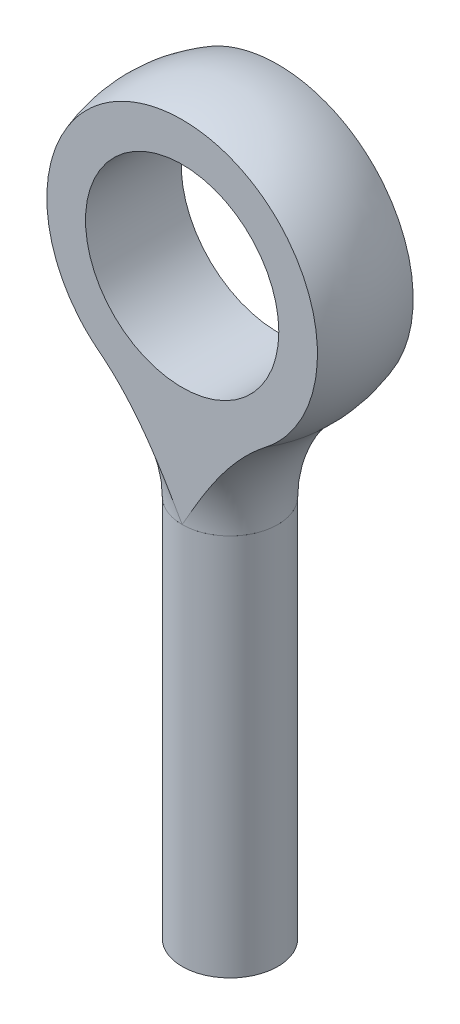
SolidWorks part; units mm, degrees
material "6061 Alloy"
ref_plane "Front" through (0, 0, 0) normal (0, 0, 1) x (1, 0, 0)
ref_plane "Top" through (0, 0, 0) normal (0, 1, 0) x (1, 0, 0)
ref_plane "Right" through (0, 0, 0) normal (1, 0, 0) x (0, 0, -1)
sketch "Sketch1" plane through (0, 0, 0) normal (0, 0, 1) x (1, 0, 0)
  line L0 (0, 0) -> (0, -25.4)
  line L1 (0, -25.4) -> (3.175, -25.4)
  line L2 (3.175, -25.4) -> (3.175, 0)
  line L3 (3.175, 0) -> (0, 0)
  line L5 (0, 23.8125) -> (0, 0) construction
  line L6 (0, 23.8125) -> (9.525, 23.8125) construction
  line L7 (9.525, 23.8125) -> (9.525, 14.2875) construction
  line L8 (-3.175, -25.4) -> (-3.175, 0) construction
  line L9 (3.2732, -25.3433) -> (3.2732, -26.2501)
  line L10 (3.2732, -26.2501) -> (2.4879, -25.7967)
  line L11 (2.586, -25.8534) -> (2.586, -25.74)
  line L12 (2.4879, -25.7967) -> (3.2732, -25.3433)
  line L13 (3.2241, -25.3717) -> (3.2241, -26.2218)
  line L14 (3.2732, -25.7967) -> (3.175, -25.7967)
  line L15 (3.175, -25.4) -> (3.175, -26.1934)
  line L16 (2.4879, -25.7967) -> (2.586, -25.7967)
  arc A0 (6.3827, 7.2174) -> (0, 23.8125) centre (0, 14.2875) ccw construction
  circle A1 centre (0, 14.2875) radius 3.175 construction
  circle A2 centre (0, 14.2875) radius 6.35 construction
  circle A3 centre (0, 14.2875) radius 6.4135 construction
  arc A4 (3.175, 0) -> (6.3827, 7.2174) centre (12.8984, 0) cw construction
  point P24 (0, 20.6375)
  point P26 (3.175, -25.7967)
  point P28 (3.2241, -25.7967)
  dimension "A" = 6.35
  dimension "Ball Dia" = 12.7
  dimension "B" = 19.05
  dimension "D1" = 12.827
  dimension "D" = 39.6875
  dimension "E" = 25.4
  dimension "Thread Dia" = 6.35
  dimension "D2" = 60
  dimension "Pitch" = 0.9068
  dimension "D4" = 0.1133
sketch "Sketch2" plane through (0, 0, 0) normal (1, 0, 0) x (0, 0, -1)
  line L0 (3.175, 14.2875) -> (-3.175, 14.2875)
  line L1 (3.175, 15.0498) -> (0, 14.2875) construction
  line L2 (3.175, 13.5252) -> (0, 14.2875) construction
  line L6 (4.7625, 14.2875) -> (-4.7625, 14.2875)
  line L7 (0, 11.1125) -> (0, 17.4625)
  line L8 (0, 23.8125) -> (0, 0) construction
  line L9 (0, 17.4625) -> (0, 11.1125) construction
  circle A0 centre (0, 14.2875) radius 6.35
  circle A1 centre (0, 14.2875) radius 9.525
  point P4 (0, 14.2875)
  point P7 (0, 20.6375)
  point P9 (0, 7.9375)
  point P14 (0, 14.2875)
  point P18 (0, 14.2875)
  point P23 (9.525, 14.2875)
  point P25 (-9.525, 14.2875)
  dimension "OAWidth" = 6.35
  dimension "Swivel" = 27
  dimension "BallWidth" = 9.525
sketch "Sketch15" plane through (0, 0, 0) normal (0, 0, 1) x (1, 0, 0)
  line L0 (0, 23.8125) -> (0, 0) construction
  line L1 (9.525, 23.8125) -> (-9.525, 23.8125)
  line L2 (9.525, 23.8125) -> (9.525, 0)
  line L3 (9.525, 0) -> (-9.525, 0)
  line L4 (-9.525, 23.8125) -> (-9.525, 0)
  line L5 (3.175, 0) -> (0, 0) construction
  point P5 (0, 23.8125)
sketch "Sketch14" plane through (0, 0, 0) normal (0, 0, 1) x (1, 0, 0)
  line L1 (0, 0) -> (0, -25.4) construction
  line L2 (0, -25.4) -> (3.175, -25.4) construction
  line L3 (3.175, -25.4) -> (3.175, 0) construction
  line L5 (0, 0) -> (0, -25.4)
  line L6 (0, -25.4) -> (3.175, -25.4)
  line L7 (3.175, -25.4) -> (3.175, 0)
  line L8 (3.175, 0) -> (0, 0) construction
  line L9 (3.175, 0) -> (0, 0)
revolve "Revolve4" add sketch "Sketch14" angle 360 about L0
sketch "Sketch21" plane through (0, 0, 0) normal (0, 0, 1) x (1, 0, 0)
  line L0 (0, 23.8125) -> (0, 0) construction
  line L1 (3.175, 0) -> (0, 0) construction
  line L2 (0, 23.8125) -> (0, 0)
  line L3 (3.175, 0) -> (0, 0)
  arc A0 (6.3827, 7.2174) -> (3.175, 0) centre (12.8984, 0) ccw construction
  arc A1 (6.3827, 7.2174) -> (0, 23.8125) centre (0, 14.2875) ccw construction
  arc A2 (6.3827, 7.2174) -> (3.175, 0) centre (12.8984, 0) ccw
  arc A3 (6.3827, 7.2174) -> (0, 23.8125) centre (0, 14.2875) ccw
revolve "Revolve5" add sketch "Sketch21" angle 360 about L0
sketch "Sketch24" plane through (0, 0, 0) normal (1, 0, 0) x (0, 0, -1)
  line L0 (3.175, 14.2875) -> (3.175, 23.8125)
  line L1 (3.175, 23.8125) -> (9.525, 23.8125)
  line L2 (9.525, 0) -> (9.525, 23.8125)
  line L3 (3.175, 14.2875) -> (3.175, 0.635)
  line L4 (3.175, 0.635) -> (3.175, 0)
  line L5 (3.175, 0) -> (9.525, 0)
  line L6 (0, 23.8125) -> (0, 0) construction
  line L7 (0, 23.8125) -> (0, 0) construction
  line L8 (-3.175, 0) -> (-9.525, 0)
  line L9 (-3.175, 0.635) -> (-3.175, 0)
  line L10 (-3.175, 14.2875) -> (-3.175, 0.635)
  line L11 (-9.525, 0) -> (-9.525, 23.8125)
  line L12 (-3.175, 23.8125) -> (-9.525, 23.8125)
  line L13 (-3.175, 14.2875) -> (-3.175, 23.8125)
  dimension "D1" = 0.635
extrude "Cut-Extrude10" cut sketch "Sketch24" against normal through all both and the other way through all
sketch "Sketch17" plane through (0, 0, 0) normal (0, 0, 1) x (1, 0, 0)
  circle A2 centre (0, 14.2875) radius 6.4135 construction
  circle A3 centre (0, 14.2875) radius 6.4135
extrude "Cut-Extrude9" cut sketch "Sketch17" against normal through all both and the other way through all
sketch "Sketch7" plane through (0, 0, 0) normal (0, 0, 1) x (1, 0, 0)
  line L0 (0, 20.6375) -> (0, 7.9375)
  line L1 (0, 23.8125) -> (0, 0) construction
  line L2 (0, 0) -> (0, 7.9375) construction
  arc A0 (0, 7.9375) -> (0, 20.6375) centre (0, 14.2875) ccw
  circle A1 centre (0, 14.2875) radius 6.35 construction
revolve "Revolve3" [suppressed] add sketch "Sketch7" angle 360 about L2
sketch "Sketch10" plane through (0, 0, 0) normal (0, 0, 1) x (1, 0, 0)
  circle A0 centre (0, 14.2875) radius 3.175 construction
  circle A1 centre (0, 14.2875) radius 3.175
extrude "Cut-Extrude4" [suppressed] cut sketch "Sketch10" against normal through all and the other way through all
sketch "Sketch22" plane through (0, 0, 0) normal (0, 0, 1) x (1, 0, 0)
  line L0 (-9.525, 23.8125) -> (-9.525, 0) construction
  line L1 (9.525, 0) -> (-9.525, 0) construction
  line L2 (9.525, 23.8125) -> (9.525, 0) construction
  line L3 (9.525, 23.8125) -> (-9.525, 23.8125) construction
  line L4 (-9.525, 23.8125) -> (-9.525, 0)
  line L5 (9.525, 0) -> (-9.525, 0)
  line L6 (9.525, 23.8125) -> (9.525, 0)
  line L7 (9.525, 23.8125) -> (-9.525, 23.8125)
extrude "Cut-Extrude7" [suppressed] cut sketch "Sketch22" against normal through all from vertex
sketch "Sketch23" plane through (0, 0, 0) normal (0, 0, 1) x (1, 0, 0)
  line L0 (-9.525, 23.8125) -> (-9.525, 0) construction
  line L1 (9.525, 0) -> (-9.525, 0) construction
  line L2 (9.525, 23.8125) -> (9.525, 0) construction
  line L3 (9.525, 23.8125) -> (-9.525, 23.8125) construction
  line L4 (-9.525, 23.8125) -> (-9.525, 0)
  line L5 (9.525, 0) -> (-9.525, 0)
  line L6 (9.525, 23.8125) -> (9.525, 0)
  line L7 (9.525, 23.8125) -> (-9.525, 23.8125)
extrude "Cut-Extrude8" [suppressed] cut sketch "Sketch23" along normal through all from vertex
chamfer "Chamfer1" [suppressed] distance 0.9068 angle 45
chamfer "Chamfer2" [suppressed] distance 0.3175 angle 45
sketch "Sketch18" [suppressed] plane through (0, -25.4, 0) normal (0, -1, 0) x (1, 0, 0)
  circle A0 centre (0, 0) radius 3.175 construction
  circle A1 centre (0, 0) radius 3.175
curve "Helix/Spiral1" [suppressed] pitch 0.9068 height 26.3068 turns 29.0112
sketch "Sketch19" [suppressed] plane through (0, 0, 0) normal (0, 0, 1) x (1, 0, 0)
  line L0 (2.586, -25.8534) -> (2.586, -25.74) construction
  line L1 (2.4879, -25.7967) -> (3.2732, -25.3433) construction
  line L2 (3.2732, -26.2501) -> (2.4879, -25.7967) construction
  line L3 (3.2241, -25.3717) -> (3.2241, -26.2218) construction
  line L4 (2.586, -25.8534) -> (2.586, -25.74)
  line L5 (2.586, -25.74) -> (3.2241, -25.3717)
  line L6 (3.2241, -26.2218) -> (2.586, -25.8534)
  line L7 (3.2241, -25.3717) -> (3.2241, -26.2218)
sweep "Cut-Sweep1" [suppressed] cut profiles "Sketch19" path "Helix/Spiral1"
ref_plane "Plane1" [suppressed] through (0, 0, 0) normal (0, 1, 0) x (1, 0, 0)
sketch "Sketch20" [suppressed] plane through (0, 0, 0) normal (0, 1, 0) x (1, 0, 0)
  circle A0 centre (0, 0) radius 3.175
extrude "Boss-Extrude2" [suppressed] add sketch "Sketch20" against normal through all draft 60
combine bodies "Combine1" [suppressed] operation type add bodies to combine 130 133
sketch "Sketch25" [suppressed] plane through (0, 0, 0) normal (0, 0, 1) x (1, 0, 0)
  line L0 (0, -25.4) -> (0, 14.2875)
  line L1 (-2.2682, -25.4) -> (2.2682, -25.4) construction
  line L2 (0, -25.4) -> (0, -7.62)
  dimension "D1" = 17.78
equation "\"D1@Sketch1\"=\"Ball Dia@Sketch1\"*1.01"
equation "\"D1\"= \"A@Sketch1\" / 20"
equation "\"D3\"= \"E@Sketch1\" + .2"
equation "\"D4@Sketch1\"=\"Pitch@Sketch1\"/8"
equation "\"D1@Chamfer1\"=\"Pitch@Sketch1\""
equation "\"D4@Helix/Spiral1\"=\"Pitch@Sketch1\""
equation "\"D3@Helix/Spiral1\"=\"E@Sketch1\"+\"Pitch@Sketch1\""
equation "\"D1@Chamfer2\"=\"A@Sketch1\"/20"
equation "\"D1@Sketch24\"=(\"OAWidth@Sketch2\"/2)/5"
